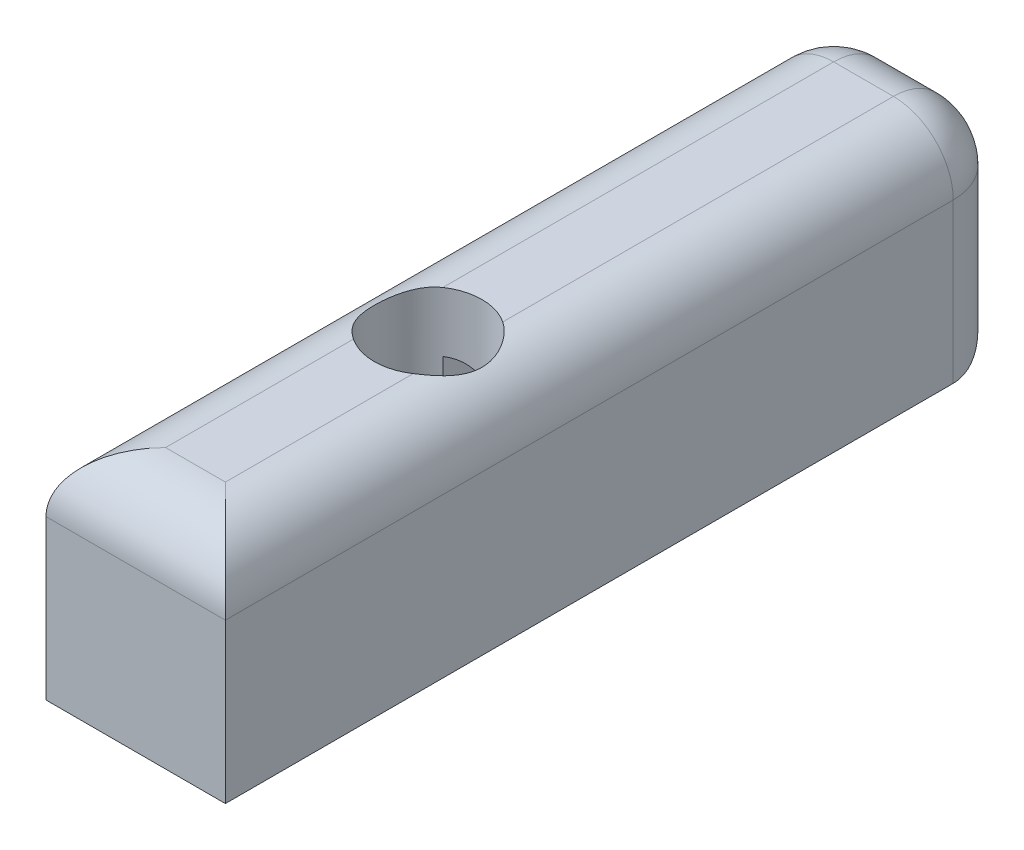
SolidWorks part; units mm, degrees
ref_plane "Front Plane" through (0, 0, 0) normal (0, 0, 1) x (1, 0, 0)
ref_plane "Top Plane" through (0, 0, 0) normal (0, 1, 0) x (1, 0, 0)
ref_plane "Right Plane" through (0, 0, 0) normal (1, 0, 0) x (0, 0, -1)
sketch "Sketch1" plane through (0, 0, 0) normal (1, 0, 0) x (0, 0, -1)
  line L1 (-48.895, 25.4386) -> (82.8131, 25.4386)
  line L2 (-48.895, 25.4386) -> (-48.895, -11.1225)
  line L3 (-48.895, -11.1225) -> (82.8131, -11.1225)
  line L4 (82.8131, 25.4386) -> (82.8131, -11.1225)
extrude "Boss-Extrude1" add sketch "Sketch1" along normal blind 30
shell "Shell1" thickness 10
sketch "Sketch2" plane through (0, 25.4386, 0) normal (0, 1, 0) x (1, 0, 0)
  line L0 (30, 82.8131) -> (0, 82.8131) construction
  line L1 (15, 0) -> (15, 82.8131) construction
  circle A0 centre (15, 0) radius 9
  dimension "D1" = 18
extrude "Cut-Extrude1" cut sketch "Sketch2" against normal through all
fillet "Fillet1" radius 10 8 edges at (30, 25.4386, -16.9591) (15, 25.4386, 48.895) (0, 25.4386, -16.9591) (15, -11.1225, -82.8131) (30, 7.1581, -82.8131) (15, 25.4386, -82.8131) (0, 7.1581, -82.8131) (20, 15.4386, -40.1482)
